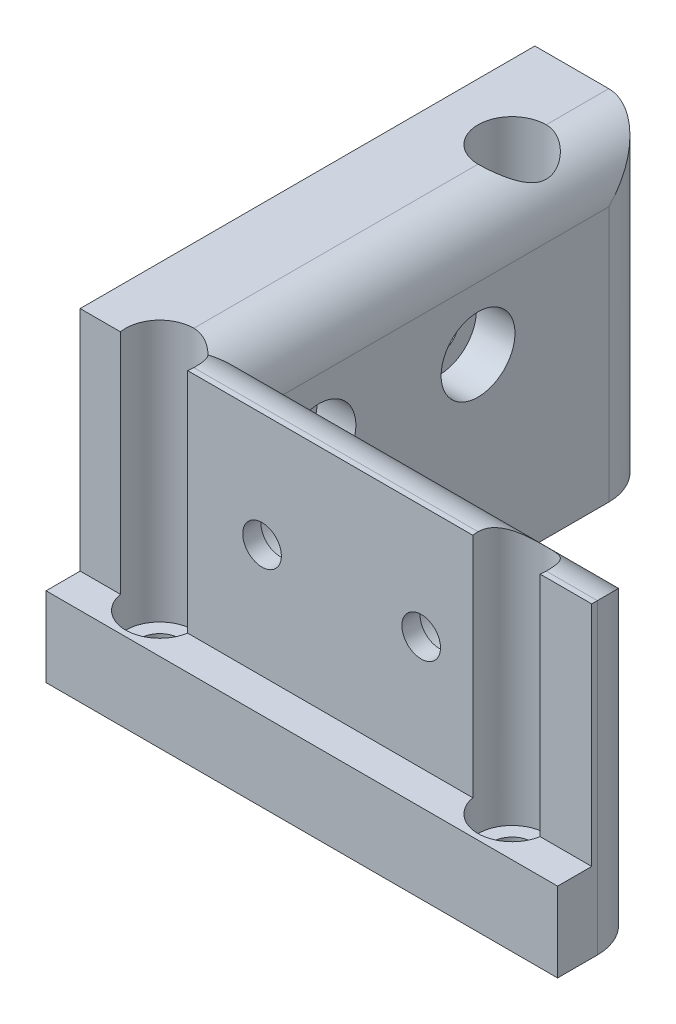
SolidWorks part; units mm, degrees
material "ABS"
ref_plane "Front Plane" through (0, 0, 0) normal (0, 0, 1) x (1, 0, 0)
ref_plane "Top Plane" through (0, 0, 0) normal (0, 1, 0) x (1, 0, 0)
ref_plane "Right Plane" through (0, 0, 0) normal (1, 0, 0) x (0, 0, -1)
sketch "Sketch1" plane through (0, 0, 0) normal (0, 1, 0) x (1, 0, 0)
  line L1 (0, 0) -> (45, 0)
  line L2 (0, 0) -> (0, 40)
  line L3 (0, 40) -> (45, 40)
  line L4 (45, 0) -> (45, 40)
  dimension "D1" = 45
  dimension "D2" = 40
extrude "Boss-Extrude1" add sketch "Sketch1" along normal blind 29
sketch "Sketch33" plane through (0, 29, 0) normal (0, 1, 0) x (1, 0, 0)
  line L0 (0, 40) -> (0, 0) construction
  line L1 (45, 0) -> (11, 0)
  line L2 (45, 0) -> (45, 35)
  line L3 (45, 35) -> (11, 35)
  line L4 (11, 0) -> (11, 35)
  line L5 (45, 40) -> (0, 40) construction
  dimension "D1" = 11
  dimension "D2" = 5
extrude "Cut-Extrude7" cut sketch "Sketch33" against normal through all
sketch "Sketch39" plane through (0, 0, -40) normal (0, 0, -1) x (-1, 0, 0)
  line L0 (0, 29) -> (0, 0) construction
  line L1 (-45, 0) -> (0, 0)
  line L2 (-45, 0) -> (-45, 9)
  line L3 (-45, 9) -> (0, 9)
  line L4 (0, 0) -> (0, 9)
  dimension "D1" = 9
extrude "Boss-Extrude2" add sketch "Sketch39" along normal blind 3
sketch "Sketch21" plane through (0, 29, 0) normal (0, 1, 0) x (1, 0, 0)
  line L0 (45, 40) -> (0, 40) construction
  circle A1 centre (6.5, 39.5) radius 1.75
  circle A2 centre (6.5, 8.5) radius 1.75
  circle A3 centre (37.5, 39.5) radius 1.75
  dimension "D3" = 0.5
  dimension "D4" = 3.5
  dimension "D7" = 3.5
  dimension "D8" = 3.5
  dimension "D1" = 0.5
  dimension "D2" = 31
extrude "Cut-Extrude6" cut sketch "Sketch21" against normal through all both and the other way through all
sketch "Sketch34" plane through (0, 29, 0) normal (0, 1, 0) x (1, 0, 0)
  circle A0 centre (6.5, 8.5) radius 3
  circle A1 centre (6.5, 39.5) radius 3
  circle A2 centre (37.5, 39.5) radius 3
  dimension "D1" = 6
  dimension "D2" = 6
  dimension "D3" = 6
extrude "Cut-Extrude8" cut sketch "Sketch34" against normal blind 23
hole_wizard "CBORE for M3 Hex Socket Head Cap Screw1" positions "Sketch35" profile "Sketch36" counterbore size "M3" standard "ISO" end condition through all
sketch "Sketch35" plane through (11, 0, 0) normal (1, 0, 0) x (0, 0, -1)
  line L1 (0, 0) -> (0, 29) construction
  line L2 (35, 0) -> (35, 29) construction
  line L3 (35, 29) -> (0, 29) construction
  point P0 (16, 19)
  point P2 (30, 19)
  dimension "D1" = 10
  dimension "D2" = 10
  dimension "D3" = 16
  dimension "D4" = 5
sketch "Sketch36" plane through (11, 19, -16) normal (0, 1, 0) x (0, 0, -1)
  line L0 (0, 0) -> (0, 11)
  line L1 (0, 11) -> (1.7, 11)
  line L3 (1.7, 11) -> (1.7, 3.4)
  line L4 (1.7, 3.4) -> (3.25, 3.4)
  line L5 (3.25, 3.4) -> (3.25, 0)
  line L7 (3.25, 0) -> (0, 0)
  line L11 (0, -6.35) -> (0, 107.95) construction
  dimension "Thru Hole Dia." = 3.4
  dimension "Thru Hole Depth" = 11
  dimension "C'Bore Dia." = 6.5
  dimension "C'Bore Depth" = 3.4
hole_wizard "CBORE for M3 Hex Socket Head Cap Screw2" positions "Sketch37" profile "Sketch38" counterbore size "M3" standard "ISO" end condition through all
sketch "Sketch37" plane through (0, 0, -35) normal (0, 0, 1) x (1, 0, 0)
  line L1 (11, 0) -> (11, 29) construction
  line L2 (45, 0) -> (45, 29) construction
  line L3 (45, 29) -> (11, 29) construction
  point P0 (16, 19)
  point P2 (30, 19)
  dimension "D1" = 10
  dimension "D2" = 10
  dimension "D3" = 5
  dimension "D4" = 15
sketch "Sketch38" plane through (16, 19, -35) normal (1, 0, 0) x (0, -1, 0)
  line L0 (0, 0) -> (0, 8)
  line L1 (0, 8) -> (1.7, 8)
  line L3 (1.7, 8) -> (1.7, 3.4)
  line L4 (1.7, 3.4) -> (3.25, 3.4)
  line L5 (3.25, 3.4) -> (3.25, 0)
  line L7 (3.25, 0) -> (0, 0)
  line L11 (0, -6.35) -> (0, 107.95) construction
  dimension "Thru Hole Dia." = 3.4
  dimension "Thru Hole Depth" = 8
  dimension "C'Bore Dia." = 6.5
  dimension "C'Bore Depth" = 3.4
fillet "Fillet1" radius 4.5 4 edges at (11, 14.5, 0) (45, 14.5, -35) (28, 29, -35) (11, 29, -17.5)
sketch "Sketch40" plane through (0, 0, 0) normal (-1, 0, 0) x (0, 0, 1)
  line L0 (-43, 0) -> (-43, 9) construction
  line L1 (-43, 2) -> (0, 2)
  line L2 (-43, 2) -> (-43, 0)
  line L3 (-43, 0) -> (0, 0)
  line L4 (0, 2) -> (0, 0)
  dimension "D1" = 2
extrude "Cut-Extrude9" cut sketch "Sketch40" against normal through all
sketch "Sketch41" plane through (0, 29, 0) normal (0, 1, 0) x (1, 0, 0)
  line L0 (3.542, 40) -> (0, 40) construction
  line L1 (0, 0) -> (6, 0)
  line L2 (0, 0) -> (0, 40)
  line L3 (0, 40) -> (6, 40)
  line L4 (6, 0) -> (6, 40)
  dimension "D1" = 6
extrude "Cut-Extrude10" [suppressed] cut sketch "Sketch41" against normal blind 20
mirror "Mirror1" about plane through (0, 29, 0) normal (0, 0, -1) of bodies 125 122
delete or keep bodies "Body-Delete/Keep 1" type delete bodies bodies 125
